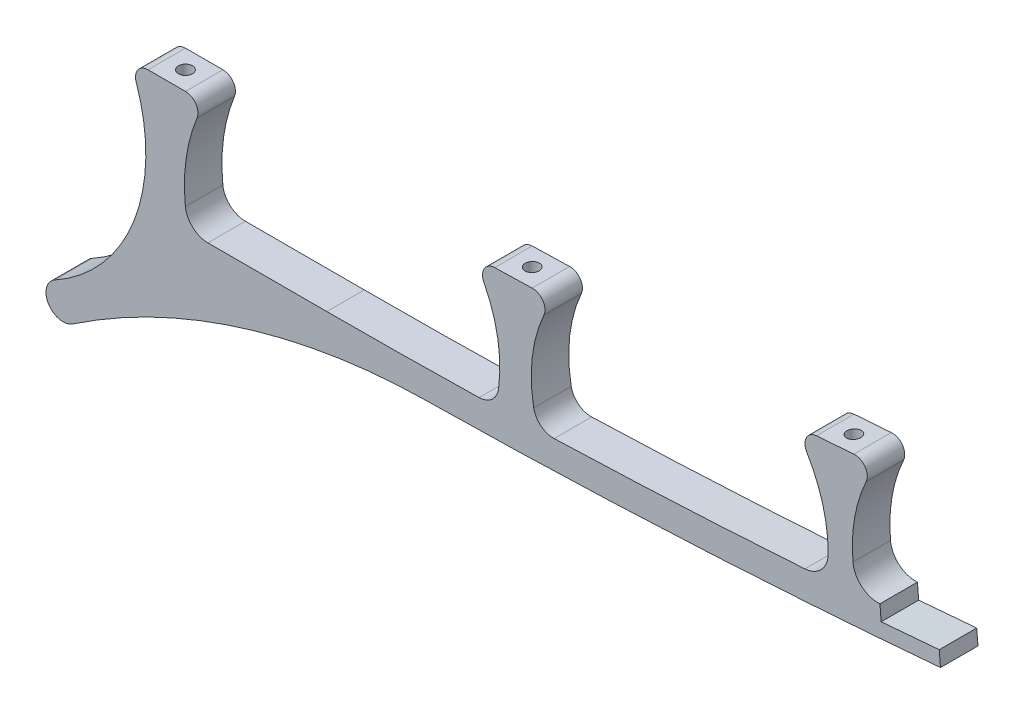
SolidWorks part; units mm, degrees
ref_plane "Front Plane" through (0, 0, 0) normal (0, 0, 1) x (1, 0, 0)
ref_plane "Top Plane" through (0, 0, 0) normal (0, 1, 0) x (1, 0, 0)
ref_plane "Right Plane" through (0, 0, 0) normal (1, 0, 0) x (0, 0, -1)
sketch "Sketch1" plane through (0, 0, 4.0971) normal (0, 0, -1) x (-1, 0, 0)
  line L0 (-62.7619, -51.7222) -> (-58.001, -51.5972) construction
  line L1 (-62.7619, -51.7222) -> (-58.001, -51.5972)
  line L2 (-250.1152, -63.0874) -> (-250.684, -56.8905) construction
  line L3 (-250.1152, -63.0874) -> (-250.684, -56.8905)
  line L4 (5.0134, -50.6875) -> (4.8506, -13.0704)
  line L5 (293.8258, -32.3629) -> (292.5411, -55.9947)
  line L6 (459.2981, -30.7507) -> (468.8231, -30.7507)
  line L7 (423.3798, -61.2307) -> (453.91, -61.2307)
  line L10 (423.2417, -37.1007) -> (607.4086, -37.1007) construction
  line L11 (270.0646, -24.076) -> (423.3798, -30.7507) construction
  line L12 (269.6518, -30.414) -> (423.1036, -37.0947) construction
  line L13 (270.0646, -24.076) -> (423.3798, -30.7507) construction
  line L14 (269.6518, -30.414) -> (423.2417, -37.1007) construction
  line L15 (270.0646, -24.076) -> (423.3798, -30.7507) construction
  line L16 (268.1133, -54.0366) -> (422.0742, -60.7394) construction
  line L17 (268.1133, -54.0366) -> (282.8559, -55.2703)
  line L39 (464.0606, -30.7507) -> (464.0606, -61.2307)
  line L43 (423.3798, -61.2307) -> (607.4086, -61.2307) construction
  line L44 (375.9837, -30.118) -> (375.1663, -60.587)
  line L45 (423.3798, -30.7507) -> (607.4086, -30.7507) construction
  arc A10 (295.9963, -50.7756) -> (301.9161, -57.1188) centre (302.3463, -50.7834) ccw
  arc A11 (301.4662, -31.1688) -> (298.9719, -26.3615) centre (298.7477, -29.5285) ccw
  arc A12 (289.4896, -25.6646) -> (286.3657, -30.1613) centre (289.2483, -28.8304) ccw
  arc A13 (282.8559, -55.2703) -> (289.7096, -49.5155) centre (283.3855, -48.9424) ccw
  arc A17 (301.4662, -31.1688) -> (295.9963, -50.7756) centre (334.0387, -50.8222) ccw
  arc A18 (289.7096, -49.5155) -> (286.3657, -30.1613) centre (251.8722, -46.0867) ccw
  circle A19 centre (490.3927, -92.6507) radius 4.3495
  arc A24 (383.4811, -34.8689) -> (379.749, -56.3925) centre (415.8403, -51.5652) ccw
  circle A29 centre (384.8064, -55.7161) radius 5.1024
  arc A30 (471.8244, -34.9614) -> (468.8231, -30.7507) centre (468.8231, -33.9257) ccw
  arc A31 (459.2981, -30.7507) -> (456.3562, -35.1198) centre (459.2981, -33.9257) ccw
  circle A32 centre (453.6208, -55.4881) radius 5.7427
  arc A33 (383.4811, -34.8689) -> (380.7361, -30.239) centre (380.6595, -33.4131) ccw
  arc A36 (459.3328, -56.0812) -> (456.3562, -35.1198) centre (415.8403, -51.5652) ccw
  arc A39 (368.2424, -34.4601) -> (371.2316, -29.9841) centre (371.1379, -33.1577) cw
  arc A40 (368.2424, -34.4601) -> (370.815, -56.1528) centre (335.0345, -49.3973) cw
  circle A41 centre (365.8012, -55.2062) radius 5.1024
  arc A42 (487.9615, -96.2573) -> (398.3517, -68.1968) centre (396.0818, -232.558) ccw
  arc A43 (471.8244, -34.9614) -> (492.4999, -88.8458) centre (514.2362, -49.5967) ccw
  spline S20 degree 1 poles (366398.024, 9576.3228) (-366524.7965, -9679.8002) knots -76971.699337 -76971.699337 76975.961644 76975.961644 only from (-53.2401, -51.4722) to (-58.001, -51.5972) construction
  spline S21 degree 1 poles (-53.2401, -51.4722) (-58.001, -51.5972) knots 0 0 1 1
  spline S22 degree 3 poles (-366283.8205, -17716.948) (-122202.6297, -5946.5803) (121970.8169, 5839.1835) (366052.004, 17609.5507) knots -76977.855707 -76977.855707 -76977.855707 -76977.855707 76982.000972 76982.000972 76982.000972 76982.000972 only from (-125.7663, -54.1741) to (-121.0093, -53.9446) construction
  spline S23 degree 1 poles (366035.5792, 17611.4947) (-366288.3596, -17719.9032) knots -76971.699337 -76971.699337 76975.961644 76975.961644 only from (-116.2524, -53.7151) to (-121.0093, -53.9446) construction
  spline S24 degree 3 poles (-125.7663, -54.1741) (-124.1807, -54.0976) (-122.595, -54.0211) (-121.0093, -53.9446) knots 0 0 0 0 1 1 1 1
  spline S25 degree 1 poles (-116.2524, -53.7151) (-121.0093, -53.9446) knots 0 0 1 1
  spline S26 degree 3 poles (-365864.3718, -25779.0387) (-122073.8662, -8605.5374) (121716.5905, 8490.9359) (365507.0964, 25664.4407) knots -76971.699337 -76971.699337 -76971.699337 -76971.699337 76975.961644 76975.961644 76975.961644 76975.961644 only from (-188.7625, -58.0119) to (-184.0117, -57.678) construction
  spline S27 degree 1 poles (365496.3363, 25644.4265) (-365875.1074, -25760.538) knots -76971.699337 -76971.699337 76975.961644 76975.961644 only from (-179.2609, -57.3441) to (-184.0117, -57.678) construction
  spline S28 degree 3 poles (-188.7625, -58.0119) (-187.1789, -57.9006) (-185.5953, -57.7893) (-184.0117, -57.678) knots 0 0 0 0 1 1 1 1
  spline S29 degree 1 poles (-179.2609, -57.3441) (-184.0117, -57.678) knots 0 0 1 1
  spline S30 degree 3 poles (-365301.3101, -33565.7342) (-121968.4672, -11235.1782) (121487.2779, 11110.751) (364820.1161, 33441.3066) knots -76979.795154 -76979.795154 -76979.795154 -76979.795154 76983.809836 76983.809836 76983.809836 76983.809836 only from (-250.1152, -63.0874) to (-245.3727, -62.6521) construction
  spline S31 degree 1 poles (364802.8942, 33440.7494) (-365304.3687, -33567.0383) knots -76971.699337 -76971.699337 76975.961644 76975.961644 only from (-240.6301, -62.2168) to (-245.3727, -62.6521) construction
  spline S32 degree 3 poles (-250.1152, -63.0874) (-248.5344, -62.9423) (-246.9535, -62.7972) (-245.3727, -62.6521) knots 0 0 0 0 1 1 1 1
  spline S33 degree 1 poles (-240.6301, -62.2168) (-245.3727, -62.6521) knots 0 0 1 1
  spline S34 degree 3 poles (-351120.2294, 74427.9388) (10494.0217, 34620.9522) (5972.352, 298.9935) (-6644.5567, -363.006) (-14732.5977, 33292.3398) (340712.2066, 110676.7005) knots -40.409558 -40.409558 -40.409558 -40.409558 0.498012 0.498012 41.40254 41.40254 41.40254 41.40254 only from (-260.2582, -26.3703) to (-413.5099, -34.3711) construction
  spline S35 degree 3 poles (-260.2582, -26.3703) (-285.573, -28.8027) (-310.9405, -30.6861) (-362.0399, -33.3672) (-387.7725, -34.1516) (-413.5099, -34.3711) knots 0.333333 0.333333 0.333333 0.333333 0.498012 0.498012 0.664679 0.664679 0.664679 0.664679
  spline S36 degree 3 poles (350477.0671, 77415.5224) (-10783.169, 34525.5553) (-5964.8095, 247.3458) (6657.3809, -305.4861) (14454.3598, 33422.1949) (-341643.6335, 107772.7294) knots -40.405514 -40.405514 -40.405514 -40.405514 0.5 0.5 41.406764 41.406764 41.406764 41.406764 only from (270.0646, -24.076) to (423.3798, -30.7507) construction
  spline S37 degree 3 poles (270.0646, -24.076) (295.3995, -26.2893) (320.7823, -27.9531) (371.903, -30.1921) (397.6415, -30.7539) (423.3798, -30.7507) knots 0.335321 0.335321 0.335321 0.335321 0.5 0.5 0.666667 0.666667 0.666667 0.666667
  spline S38 degree 3 poles (34216.6622, 363348.8873) (5327.7801, -4762.6903) (2936.3737, -226.3591) (225.9514, -20.5338) (214.915, -19.7614) (181.7932, -17.6233) (159.6926, -16.4536) (115.476, -14.6188) (93.3552, -13.9534) (60.1689, -13.3398) (49.1062, -13.195) (-2720.7868, 6.5962) (-5526.344, -4450.3222) (-4429.285, 364973.5107) knots -30.461707 -30.461707 -30.461707 -30.461707 0.125 0.125 0.25 0.25 0.5 0.5 0.75 0.75 0.875 0.875 32.045674 32.045674 32.045674 32.045674 only from (270.0646, -24.076) to (4.8506, -13.0704) construction
  spline S39 degree 3 poles (-37282.4943, 363051.1607) (-5277.6718, -4808.7913) (-2924.7638, -251.7198) (-216.1773, -22.4465) (-205.1481, -21.5787) (-172.0462, -19.1541) (-149.9564, -17.7933) (-105.7573, -15.5759) (-83.6432, -14.7191) (-50.4634, -13.8184) (-39.4023, -13.5779) (2730.1506, 30.1779) (5573.6801, -4402.0973) (1314.8646, 364983.8749) knots -30.462296 -30.462296 -30.462296 -30.462296 0.125 0.125 0.25 0.25 0.5 0.5 0.75 0.75 0.875 0.875 32.044896 32.044896 32.044896 32.044896 only from (-260.2582, -26.3703) to (4.8506, -13.0704) construction
  spline S40 degree 3 poles (270.0646, -24.076) (259.0414, -23.1193) (248.0148, -22.2092) (225.9514, -20.5338) (214.915, -19.7614) (181.7932, -17.6233) (159.6926, -16.4536) (115.476, -14.6188) (93.3552, -13.9534) (60.1689, -13.3398) (49.1062, -13.195) (26.9794, -13.0369) (15.9153, -13.0299) (4.8506, -13.0704) knots 0 0 0 0 0.125 0.125 0.25 0.25 0.5 0.5 0.75 0.75 0.875 0.875 1 1 1 1
  spline S41 degree 3 poles (-260.2582, -26.3703) (-249.2437, -25.3183) (-238.2254, -24.3128) (-216.1773, -22.4465) (-205.1481, -21.5787) (-172.0462, -19.1541) (-149.9564, -17.7933) (-105.7573, -15.5759) (-83.6432, -14.7191) (-50.4634, -13.8184) (-39.4023, -13.5779) (-17.2777, -13.2284) (-6.214, -13.1256) (4.8506, -13.0704) knots 0 0 0 0 0.125 0.125 0.25 0.25 0.5 0.5 0.75 0.75 0.875 0.875 1 1 1 1
  spline S42 degree 1 poles (266.8016, -61.5516) (423.3844, -68.3681) knots 0 0 1 1 construction
  spline S43 degree 1 poles (266.8016, -61.5516) (5.0134, -50.6875) knots 0 0 1 1 construction
  spline S44 degree 1 poles (-256.671, -63.8163) (5.0134, -50.6875) knots 0 0 1 1 construction
  spline S45 degree 1 poles (-256.671, -63.8163) (-413.1891, -71.9871) knots 0 0 1 1 construction
  spline S46 degree 3 poles (423.3844, -68.3681) (417.128, -68.3689) (406.6951, -68.3157) (354.4413, -67.5941) (308.4593, -65.1906) (266.8016, -61.5516) knots 0.335344 0.335344 0.335344 0.335344 0.375021 0.401473 0.666667 0.666667 0.666667 0.666667
  spline S47 degree 3 poles (266.8016, -61.5516) (261.3509, -61.0786) (250.4335, -60.154) (228.7012, -58.4345) (190.549, -55.7631) (136.0425, -52.8693) (81.4825, -51.2368) (43.241, -50.7379) (21.4384, -50.6506) (10.4839, -50.6675) (5.0134, -50.6875) knots 0.00004 0.00004 0.00004 0.00004 0.062532 0.125024 0.250007 0.499973 0.749939 0.874922 0.937414 0.999905 0.999905 0.999905 0.999905
  spline S48 degree 3 poles (5.0134, -50.6875) (-0.4572, -50.7148) (-11.4114, -50.7928) (-33.2124, -51.0686) (-71.4483, -51.8985) (-125.9921, -54.0029) (-180.4716, -57.3683) (-218.5991, -60.3696) (-240.3157, -62.2771) (-251.2247, -63.2961) (-256.671, -63.8163) knots 0.00004 0.00004 0.00004 0.00004 0.062532 0.125023 0.250007 0.499973 0.749939 0.874922 0.937414 0.999905 0.999905 0.999905 0.999905
  spline S49 degree 3 poles (-256.671, -63.8163) (-308.6753, -68.8128) (-360.9473, -71.5416) (-413.1891, -71.9871) knots 0.333356 0.333356 0.333356 0.333356 0.664679 0.664679 0.664679 0.664679
  spline S50 degree 1 poles (267.412, -54.4403) (423.3798, -61.2307) knots 0 0 1 1 construction
  spline S51 degree 1 poles (268.1133, -54.0366) (4.9805, -43.0872) knots 0 0 1 1 construction
  spline S52 degree 1 poles (-257.3958, -56.2506) (4.9805, -43.0872) knots 0 0 1 1 construction
  spline S53 degree 1 poles (-257.3958, -56.2506) (-413.254, -64.3871) knots 0 0 1 1 construction
  spline S54 degree 3 poles (267.412, -54.4403) (276.0285, -55.1931) (290.4062, -56.3442) (313.5674, -57.917) (336.8899, -59.2149) (356.0529, -59.9983) (367.2252, -60.3576) (370.4015, -60.4534) (373.5779, -60.5449) (376.7545, -60.6301) (379.9313, -60.709) (383.1082, -60.7837) (397.5889, -61.095) (411.2827, -61.2322) (423.3798, -61.2307) knots 0.335321 0.335321 0.335321 0.335321 0.390393 0.427108 0.483088 0.539068 0.549181 0.554238 0.559295 0.569408 0.574465 0.579521 0.589635 0.666659 0.666659 0.666659 0.666659 only from (301.9161, -57.1188) to (423.3798, -61.2307)
  spline S55 degree 3 poles (268.1133, -54.0366) (262.6347, -53.5611) (251.6633, -52.6287) (229.8118, -50.8954) (191.4718, -48.2039) (136.6796, -45.2869) (81.8357, -43.6415) (43.4028, -43.1385) (21.4808, -43.0503) (10.477, -43.0671) (4.9805, -43.0872) knots -0.002434 -0.002434 -0.002434 -0.002434 0.060213 0.122861 0.248155 0.498745 0.749335 0.87463 0.937277 0.999924 0.999924 0.999924 0.999924
  spline S56 degree 3 poles (4.9805, -43.0872) (-0.5025, -43.1146) (-11.479, -43.1927) (-33.3456, -43.4694) (-71.6781, -44.3013) (-126.3714, -46.4114) (-181.0006, -49.7861) (-219.224, -52.795) (-241.0064, -54.7082) (-251.9372, -55.7293) (-257.3958, -56.2506) knots 0.000032 0.000032 0.000032 0.000032 0.062525 0.125019 0.250005 0.499978 0.749951 0.874938 0.937431 0.999924 0.999924 0.999924 0.999924
  spline S57 degree 3 poles (-257.3958, -56.2506) (-309.1808, -61.2261) (-361.2324, -63.9435) (-413.254, -64.3871) knots 0.333351 0.333351 0.333351 0.333351 0.664679 0.664679 0.664679 0.664679
  spline S59 degree 3 poles (-413.1844, -71.9874) (-456.1014, -80.1224) (-434.4954, -79.3287) (-479.9907, -101.3371) (-478.4868, -100.9323) knots 0 0 0 0 0.938514 1 1 1 1
  spline S61 degree 1 poles (269.6518, -30.414) (4.8739, -19.4204) knots 0 0 1 1 construction
  spline S63 degree 3 poles (4.8739, -19.4204) (26.9656, -19.3394) (71.1539, -19.6344) (137.3995, -21.6337) (203.5831, -25.1323) (247.6429, -28.5039) (269.6518, -30.414) knots -0.000515 -0.000515 -0.000515 -0.000515 0.249614 0.499743 0.749871 1 1 1 1
  spline S66 degree 1 poles (269.6518, -30.414) (4.8739, -19.4204) knots 0 0 1 1 construction
  spline S68 degree 3 poles (4.8739, -19.4204) (26.9656, -19.3394) (71.1539, -19.6344) (137.3995, -21.6337) (203.5831, -25.1323) (247.6429, -28.5039) (269.6518, -30.414) knots -0.000515 -0.000515 -0.000515 -0.000515 0.249614 0.499743 0.749871 1 1 1 1
  point P81 (310.3019, -33.4897)
  dimension "D3" = 30.48
  dimension "D5" = 6.35
  dimension "D8" = 4.7625
  dimension "D9" = 3.175
  dimension "D10" = 9.525
  dimension "D11" = 12.7
  dimension "D12" = 19.05
  dimension "D16" = 12.7
  dimension "D17" = 3.175
  dimension "D18" = 4.7625
  dimension "D19" = 4.7625
  dimension "D13" = 9.525
  dimension "D14" = 4.7625
  dimension "D15" = 25.4
  dimension "D1" = 37.6174
  dimension "D7" = 6.35
  dimension "D22" = 6.35
extrude "Boss-Extrude5" add sketch "Sketch1" along normal blind 4.7625 and the other way blind 4.7625 contours L7 S54 A10 A17 A11 S37 A12 A18 A13 L17 S55 | A19 | A19 | S54 L44 S37 | L44 S54 A29 A24 A33 S37 region at (-287.273, -56.7987, 4.0971) region at (-490.3927, -92.6507, 4.0971) region at (-372.7453, -43.9651, 4.0971) region at (-378.475, -44.1188, 4.0971)
ref_plane "Plane1" through (0.3209, -4.3662, 0) normal (-0.0733, 0.9973, 0) x (0.9973, 0.0733, 0)
sketch "Sketch6" plane through (0.3209, -4.3662, 0) normal (-0.0733, 0.9973, 0) x (0.9973, 0.0733, 0)
  line L0 (-295.346, 0.6654) -> (-295.346, -8.8596) construction
  line L1 (-290.592, -4.0971) -> (-300.0999, -4.0971) construction
  line L4 (-290.592, -8.8596) -> (-290.592, 0.6654)
  line L10 (-300.0999, 0.6654) -> (-300.0999, -8.8596)
  line L24 (-290.592, -8.8596) -> (-290.592, 0.6654)
  line L27 (-290.592, 0.6654) -> (-300.0999, 0.6654)
  line L29 (-290.592, 0.6654) -> (-300.0999, 0.6654)
  line L30 (-300.0999, -8.8596) -> (-290.592, -8.8596)
  line L31 (-300.0999, -8.8596) -> (-290.592, -8.8596)
  line L34 (-300.0999, 0.6654) -> (-300.0999, -8.8596)
  circle A0 centre (-295.346, -4.0971) radius 1.778
  point P6 (-290.592, -4.0971)
  point P7 (-295.346, 0.6654)
  point P13 (-295.346, -4.0971)
  dimension "D1" = 0
extrude "Cut-Extrude3" cut sketch "Sketch6" against normal through all contours A0
ref_axis "Axis1" through (-291.4807, -63.4328, 4.0971) along (-0.0733, 0.9973, 0)
ref_plane "Plane2" through (3.0659, -41.7188, 0) normal (-0.0733, 0.9973, 0) x (-0.9947, -0.0731, 0.0729)
sketch "Sketch7" plane through (3.0659, -41.7188, 0) normal (-0.0733, 0.9973, 0) x (-0.9947, -0.0731, 0.0729)
  circle A0 centre (294.8582, -17.4541) radius 1.778 construction
  circle A1 centre (294.8582, -17.4541) radius 1.778
  circle A2 centre (294.8582, -17.4541) radius 3.048
  dimension "D1" = 6.096
extrude "Cut-Extrude4" cut sketch "Sketch7" along normal blind 3.556 and the other way through all
mirror "Mirror4" about plane through (-4.794, 0.0207, 8.8596) normal (-1, 0.0043, 0) of "Cut-Extrude4", "Cut-Extrude3", "Boss-Extrude5"
sketch "Sketch8" plane through (0, 0, -0.6654) normal (0, 0, -1) x (-1, 0, 0)
  line L0 (-4352.3873, -105.2388) -> (-4674.1378, -106.5977)
  line L1 (-4352.3873, -105.2388) -> (-4352.7091, -29.0388)
  line L2 (-4674.1378, -106.5977) -> (-4674.4596, -30.3977)
  line L3 (-4352.7091, -29.0388) -> (-4674.4596, -30.3977)
  dimension "D1" = 76.2
  dimension "D2" = 321.7505
sketch "Sketch9" plane through (0, 0, -0.6654) normal (0, 0, -1) x (-1, 0, 0)
  line L0 (268.1133, -54.0366) -> (282.8559, -55.2703) construction
  line L1 (268.1133, -54.0366) -> (282.8559, -55.2703)
  line L2 (267.7955, -57.8333) -> (282.5382, -59.067)
  line L3 (282.5382, -59.067) -> (282.8559, -55.2703)
  line L4 (267.7955, -57.8333) -> (267.4671, -61.6096)
  line L5 (268.1133, -54.0366) -> (271.2267, -16.8305)
  line L6 (271.2267, -16.8305) -> (-501.7302, -16.8305)
  line L7 (-501.7302, -16.8305) -> (-501.7302, -147.1798)
  line L8 (-501.7302, -147.1798) -> (267.4671, -61.6096)
  spline S0 degree 3 poles (2340.1552, 397.7315) (1297.6129, 87.0856) (115.0439, -338.026) (-1058.2174, 398.7267) (-1032.0079, 1250.0528) knots -2.465055 -2.465055 -2.465055 -2.465055 0.401473 5.010775 5.010775 5.010775 5.010775 only from (398.3517, -68.1968) to (266.8016, -61.5516) construction
  spline S1 degree 3 poles (398.3517, -68.1968) (396.2658, -68.168) (352.3561, -67.4851) (308.4593, -65.1906) (266.8016, -61.5516) knots 0.388247 0.388247 0.388247 0.388247 0.401473 0.666667 0.666667 0.666667 0.666667
  dimension "D1" = 3.81
extrude "Cut-Extrude5" cut sketch "Sketch9" against normal through all contours L7 L8 L4 L2 L3 L1 L5 L6 region at (178.8306, -64.0501, -0.6654)
ref_plane "Plane3" through (0.5368, -20.0102, 0) normal (-0.0268, 0.9996, 0) x (0.9996, 0.0268, 0)
sketch "Sketch10" plane through (0.5368, -20.0102, 0) normal (-0.0268, 0.9996, 0) x (0.9996, 0.0268, 0)
  line L0 (-376.6562, 0.6654) -> (-376.6562, -8.8596) construction
  line L1 (-371.9023, -4.0971) -> (-381.4101, -4.0971) construction
  line L4 (-371.9023, -8.8596) -> (-371.9023, 0.6654)
  line L5 (-371.9023, 0.6654) -> (-381.4101, 0.6654)
  line L6 (-381.4101, 0.6654) -> (-381.4101, -8.8596)
  line L7 (-381.4101, -8.8596) -> (-371.9023, -8.8596)
  line L8 (-371.9023, -8.8596) -> (-371.9023, 0.6654)
  line L9 (-371.9023, 0.6654) -> (-381.4101, 0.6654)
  line L10 (-381.4101, 0.6654) -> (-381.4101, -8.8596)
  line L11 (-381.4101, -8.8596) -> (-371.9023, -8.8596)
  circle A0 centre (-376.6562, -4.0971) radius 1.778
  dimension "D1" = 0
extrude "Cut-Extrude6" cut sketch "Sketch10" against normal through all contours A0 region at (-375.9839, -30.1115, 4.0971)
ref_point "Point1"
ref_plane "Plane5" through (1.5458, -57.6195, 0) normal (-0.0268, 0.9996, 0) x (0.9996, 0.0268, 0)
sketch "Sketch12" plane through (1.5458, -57.6195, 0) normal (-0.0268, 0.9996, 0) x (0.9996, 0.0268, 0)
  circle A2 centre (-376.6562, -4.0971) radius 3.048
  dimension "D1" = 6.096
extrude "Cut-Extrude11" cut sketch "Sketch12" along normal blind 3.556 and the other way through all contours A2
ref_plane "Plane6" through (0, -30.7507, 0) normal (0, 1, 0) x (1, 0, 0)
sketch "Sketch13" plane through (0, -30.7507, 0) normal (0, 1, 0) x (1, 0, 0)
  line L0 (-464.0606, 0.6654) -> (-464.0606, -8.8596) construction
  line L1 (-459.2981, -4.0971) -> (-468.8231, -4.0971) construction
  line L4 (-459.2981, -8.8596) -> (-459.2981, 0.6654)
  line L5 (-459.2981, 0.6654) -> (-468.8231, 0.6654)
  line L6 (-468.8231, 0.6654) -> (-468.8231, -8.8596)
  line L7 (-468.8231, -8.8596) -> (-459.2981, -8.8596)
  line L8 (-459.2981, -8.8596) -> (-459.2981, 0.6654)
  line L9 (-459.2981, 0.6654) -> (-468.8231, 0.6654)
  line L10 (-468.8231, 0.6654) -> (-468.8231, -8.8596)
  line L11 (-468.8231, -8.8596) -> (-459.2981, -8.8596)
  circle A0 centre (-464.0606, -4.0971) radius 1.778
  dimension "D1" = 0
extrude "Cut-Extrude12" cut sketch "Sketch13" against normal through all contours A0 region at (-464.0606, -30.7507, 4.0971)
ref_plane "Plane7" through (0, -68.8507, 0) normal (0, 1, 0) x (1, 0, 0)
sketch "Sketch14" plane through (0, -68.8507, 0) normal (0, 1, 0) x (1, 0, 0)
  circle A2 centre (-464.0606, -4.0971) radius 3.048
  dimension "D1" = 6.096
extrude "Cut-Extrude13" cut sketch "Sketch14" along normal blind 3.556 and the other way through all
ref_plane "Plane8" through (0, 0, 4.0971) normal (0, 0, -1) x (-1, 0, 0)
